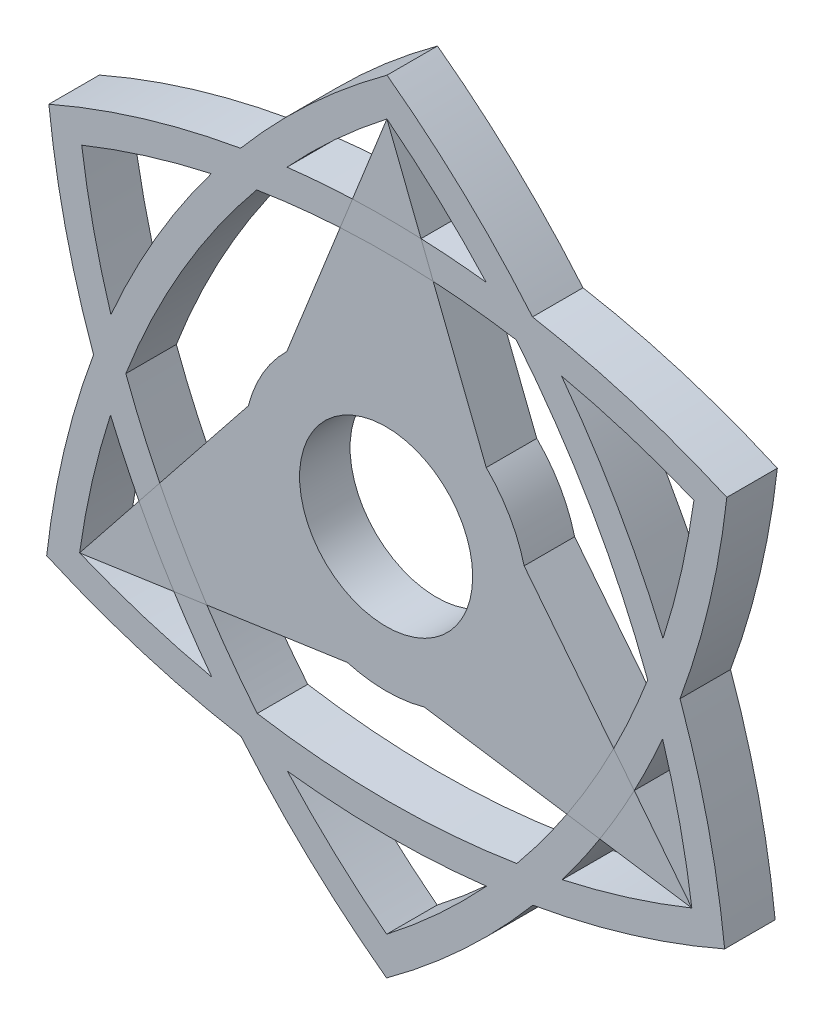
SolidWorks part; units mm, degrees
note: The reader was unsure of these and kept them because the rebuilt part matched: shared geometry of "Sketch1<4>", "Sketch1<5>".
ref_plane "Front Plane" through (0, 0, 0) normal (0, 0, 1) x (1, 0, 0)
ref_plane "Top Plane" through (0, 0, 0) normal (0, 1, 0) x (1, 0, 0)
ref_plane "Right Plane" through (0, 0, 0) normal (1, 0, 0) x (0, 0, -1)
sketch "Sketch1" plane through (0, 0, 0) normal (0, 0, 1) x (1, 0, 0)
  line L0 (-22.1734, -22.1734) -> (22.2765, -22.2765) construction
  line L1 (50.8, -50.8) -> (-50.8, -50.8) construction
  line L2 (50.8, -50.8) -> (50.8, 50.8) construction
  line L3 (50.8, 50.8) -> (-50.8, 50.8) construction
  line L4 (-50.8, -50.8) -> (-50.8, 50.8) construction
  line L5 (50.8, -50.8) -> (-50.8, 50.8) construction
  line L6 (50.8, 50.8) -> (-50.8, -50.8) construction
  line L7 (0.1032, 44.4494) -> (-38.5459, -22.1353) construction
  line L8 (-38.5459, -22.1353) -> (-25.5546, -22.1655) construction
  line L9 (38.4427, -22.3141) -> (0.1032, 44.4494) construction
  line L10 (25.7575, -22.2846) -> (38.4427, -22.3141) construction
  line L11 (0.1032, 44.4494) -> (-12.4905, 12.829)
  line L12 (0.1032, 44.4494) -> (12.5918, 12.7297)
  line L13 (-38.5459, -22.1353) -> (-17.3349, 4.4831)
  line L14 (-38.5459, -22.1353) -> (-4.865, -17.2316)
  line L15 (38.4427, -22.3141) -> (4.785, -17.254)
  line L16 (38.4427, -22.3141) -> (17.3555, 4.4026)
  circle A0 centre (0, 0) radius 10.8839
  circle A1 centre (0, 0) radius 22.2248 construction
  arc A2 (-38.5459, -22.1353) -> (-34.6562, -5.1626) centre (62.7339, -36.4138) cw
  arc A3 (0.1032, 44.4494) -> (12.5918, 32.9001) centre (-62.7348, -36.026) cw
  arc A4 (-38.5459, -22.1353) -> (-21.9026, -27.3586) centre (0.1673, 72.0922) ccw
  arc A5 (0.1125, 49.2245) -> (18.4093, 32.0408) centre (-62.7348, -36.026) cw
  arc A6 (-42.6874, -24.509) -> (-18.2412, -31.9724) centre (0.1673, 72.0922) ccw
  arc A7 (-42.6874, -24.509) -> (-36.796, 0.3173) centre (62.7339, -36.4138) cw
  arc A8 (-42.4081, 24.8039) -> (-18.3026, 32.0585) centre (0.0028, -72.4416) cw
  arc A9 (-38.2815, 22.4045) -> (-21.9829, 27.4488) centre (0.0028, -72.4416) cw
  arc A10 (42.8469, 24.6137) -> (36.9562, -0.2609) centre (-62.4071, 36.4048) cw
  arc A11 (38.7071, 22.2338) -> (34.8164, 5.2198) centre (-62.4071, 36.4048) cw
  arc A12 (-38.2815, 22.4045) -> (-34.6065, 5.7789) centre (62.6771, 36.0022) ccw
  arc A13 (-42.4081, 24.8039) -> (-36.796, 0.3173) centre (62.6771, 36.0022) ccw
  arc A14 (-12.4663, 32.9144) -> (12.5918, 32.9001) centre (0.0028, -72.4416) cw
  arc A15 (-16.2792, 28.5354) -> (16.3768, 28.5205) centre (0.0028, -72.4416) cw
  arc A16 (18.4093, 32.0408) -> (42.8469, 24.6137) centre (0.0028, -72.4416) cw
  arc A17 (22.0617, 27.4327) -> (38.7071, 22.2338) centre (0.0028, -72.4416) cw
  arc A18 (-32.7316, 0.2988) -> (-16.2093, -28.4531) centre (62.6771, 36.0022) ccw
  arc A19 (-34.6562, -5.1626) -> (-21.9026, -27.3586) centre (62.6771, 36.0022) ccw
  arc A20 (-18.2412, -31.9724) -> (0.0567, -49.1271) centre (62.6771, 36.0022) ccw
  arc A21 (-12.4148, -32.8364) -> (0.065, -44.355) centre (62.6771, 36.0022) ccw
  arc A22 (12.6152, -32.8524) -> (0.065, -44.355) centre (-62.4071, 36.4048) cw
  arc A23 (18.458, -31.9932) -> (0.0567, -49.1271) centre (-62.4071, 36.4048) cw
  arc A24 (32.8918, -0.2425) -> (16.4349, -28.4708) centre (-62.4071, 36.4048) cw
  arc A25 (34.7669, -5.722) -> (22.1451, -27.379) centre (-62.4071, 36.4048) cw
  arc A26 (-16.2093, -28.4531) -> (16.4349, -28.4708) centre (0.1673, 72.0922) ccw
  arc A27 (22.1451, -27.379) -> (38.4427, -22.3141) centre (0.1673, 72.0922) ccw
  arc A28 (-38.5459, -22.1353) -> (38.4427, -22.3141) centre (0.1673, 72.0922) ccw construction
  arc A29 (34.7669, -5.722) -> (38.4427, -22.3141) centre (-62.7348, -36.026) cw
  arc A30 (-32.7316, 0.2988) -> (-16.2792, 28.5354) centre (62.7339, -36.4138) cw
  arc A31 (0.1032, 44.4494) -> (38.4427, -22.3141) centre (-62.7348, -36.026) cw construction
  arc A32 (16.3768, 28.5205) -> (32.8918, -0.2425) centre (-62.7348, -36.026) cw
  arc A33 (-38.5459, -22.1353) -> (0.1032, 44.4494) centre (62.7339, -36.4138) cw construction
  arc A34 (-12.4663, 32.9144) -> (0.1032, 44.4494) centre (62.7339, -36.4138) cw
  arc A35 (18.458, -31.9932) -> (42.5711, -24.7077) centre (0.1673, 72.0922) ccw
  arc A36 (-12.4148, -32.8364) -> (12.6152, -32.8524) centre (0.1673, 72.0922) ccw
  arc A37 (-42.6874, -24.509) -> (42.5711, -24.7077) centre (0.1673, 72.0922) ccw construction
  arc A38 (-34.6065, 5.7789) -> (-21.9829, 27.4488) centre (62.7339, -36.4138) cw
  arc A39 (-18.3026, 32.0585) -> (0.1125, 49.2245) centre (62.7339, -36.4138) cw
  arc A40 (-42.6874, -24.509) -> (0.1125, 49.2245) centre (62.7339, -36.4138) cw construction
  arc A41 (22.0617, 27.4327) -> (34.8164, 5.2198) centre (-62.7348, -36.026) cw
  arc A42 (36.9562, -0.2609) -> (42.5711, -24.7077) centre (-62.7348, -36.026) cw
  arc A43 (0.1125, 49.2245) -> (42.5711, -24.7077) centre (-62.7348, -36.026) cw construction
  circle A44 centre (0, 0) radius 17.9052
  arc A45 (-12.4905, 12.829) -> (12.5918, 12.7297) centre (0, 0) cw
  arc A46 (-17.3349, 4.4831) -> (-4.865, -17.2316) centre (0, 0) ccw
  arc A47 (4.785, -17.254) -> (17.3555, 4.4026) centre (0, 0) ccw
  text T0 "KIRILL NEKRYUKOV\r\n"
  point P0 (0, 0)
  point P35 (0.1636, -0.0944)
  dimension "D3" = 21.7678
  dimension "D8" = 102.1024
  dimension "D9" = 106.0913
  dimension "D10" = 101.8702
  dimension "D11" = 113.4771
  dimension "D12" = 12.9913
  dimension "D13" = 5.4611
  dimension "D14" = 35.8105
  dimension "D1" = 101.6
  dimension "D2" = 101.6
  dimension "D6" = 44.45
  dimension "D7" = 66.7635
  dimension "D15" = 34.036
  dimension "D16" = 34.036
  dimension "D17" = 34.0897
  dimension "D18" = 34.036
  dimension "D19" = 34.036
  dimension "D20" = 34.036
  dimension "D4" = 3.81
  dimension "D5" = 2
extrude "Boss-Extrude6" add sketch "Sketch1" along normal blind 6.35 contours A42 A10 A16 A5 A39 A8 A13 A7 A6 A20 A23 A35 A41 A17 A11 A38 A12 A9 A14 A34 A3 L12 A15 A32 A24 L16 A25 A29 A27 L15 A26 A18 L14 A19 A4 A2 L13 A30 L11 A21 A36 | A44 A0 | A44 L13 A18 L14 | A44 L12 A15 L11 | A44 L15 A24 L16
extrude "Boss-Extrude7" add sketch "Sketch1<4>" along normal blind 6.35 separate body contours A19 L13 L14 | L11 A14 L12 | L16 A25 L15
sketch "Sketch1<4>" plane through (0, 0, 0) normal (0, 0, 1) x (1, 0, 0) same geometry as "Sketch1"
ref_plane "Plane1" through (28.6123, -9.8593, 6.35) normal (-0.6196, 0.785, 0) x (0.785, 0.6196, 0)
ref_plane "Plane2" through (-4.2318, 33.5651, 6.35) normal (-0.37, -0.929, 0) x (-0.929, 0.37, 0)
extrude "Boss-Extrude9" add sketch "Sketch1<5>" along normal through all separate body contours L11 A15 L12 A14 | L13 A19 L14 A18 | A25 L16 A24 L15
sketch "Sketch1<5>" plane through (0, 0, 0) normal (0, 0, 1) x (1, 0, 0) same geometry as "Sketch1"
